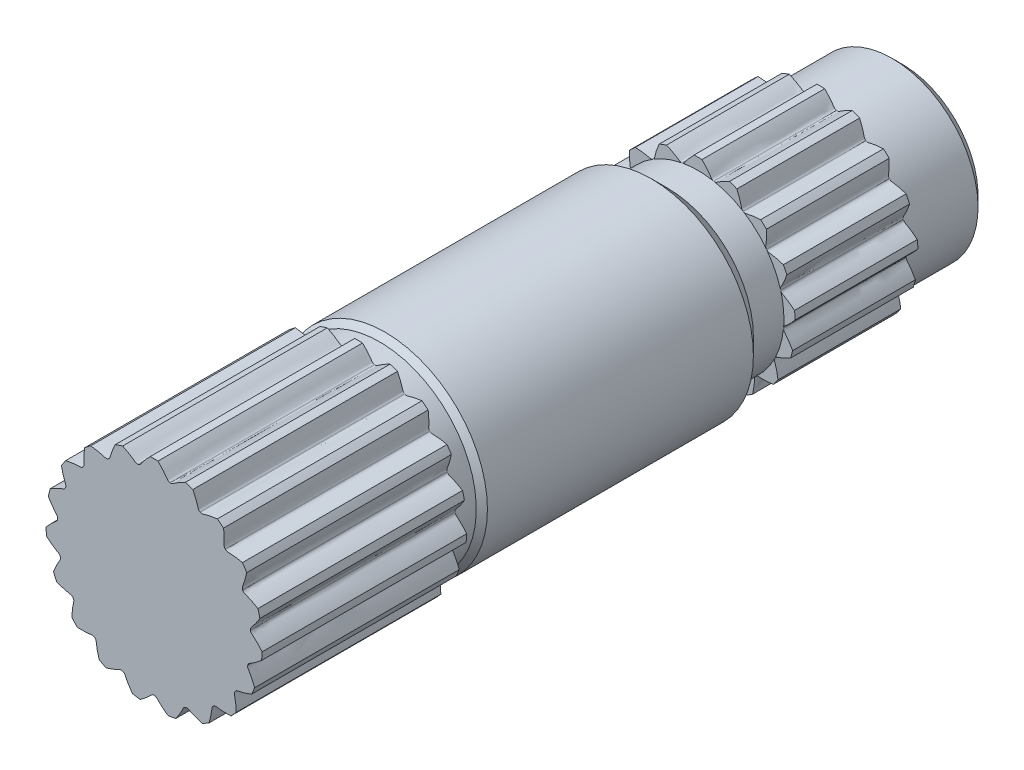
SolidWorks part; units mm, degrees
material "Alloy Steel"
ref_plane "Front Plane" through (0, 0, 0) normal (0, 0, 1) x (1, 0, 0)
ref_plane "Top Plane" through (0, 0, 0) normal (0, 1, 0) x (1, 0, 0)
ref_plane "Right Plane" through (0, 0, 0) normal (1, 0, 0) x (0, 0, -1)
sketch "Sketch12" plane through (0, 0, 0) normal (0, 0, 1) x (1, 0, 0)
  circle A0 centre (0, 0) radius 10
  dimension "D1" = 20
extrude "Boss-Extrude5" add sketch "Sketch12" along normal mid plane 30
sketch "Sketch13" plane through (0, 0, 15) normal (0, 0, 1) x (1, 0, 0)
  circle A0 centre (0, 0) radius 9.4556
  dimension "D1" = 18.9113
extrude "Boss-Extrude6" add sketch "Sketch13" along normal blind 1.587
sketch "Sketch14" plane through (0, 0, -15) normal (0, 0, -1) x (-1, 0, 0)
  circle A0 centre (0, 0) radius 8.3981
  dimension "D1" = 16.7963
extrude "Boss-Extrude7" add sketch "Sketch14" along normal blind 1.587
sketch "Sketch15" plane through (0, 0, 16.587) normal (0, 0, 1) x (1, 0, 0)
  line L0 (5.7898, -7.4758) -> (5.8078, -7.4618)
  line L1 (5.8078, -7.4618) -> (5.8257, -7.4478)
  line L2 (7.9035, -5.1908) -> (7.9159, -5.1717)
  line L3 (7.9159, -5.1717) -> (7.9284, -5.1527)
  line L4 (9.1607, -2.3432) -> (9.1663, -2.3212)
  line L5 (9.1663, -2.3212) -> (9.1719, -2.2992)
  line L6 (9.4252, 0.7582) -> (9.4233, 0.7808)
  line L7 (9.4233, 0.7808) -> (9.4214, 0.8035)
  line L8 (8.6683, 3.7775) -> (8.6592, 3.7983)
  line L9 (8.6592, 3.7983) -> (8.6501, 3.8191)
  line L10 (6.9721, 6.3874) -> (6.9567, 6.4041)
  line L11 (6.9567, 6.4041) -> (6.9413, 6.4208)
  line L12 (4.5204, 8.3051) -> (4.5004, 8.316)
  line L13 (4.5004, 8.316) -> (4.4804, 8.3268)
  line L14 (1.5788, 9.3229) -> (1.5563, 9.3267)
  line L15 (1.5563, 9.3267) -> (1.5339, 9.3304)
  line L16 (-1.5339, 9.3304) -> (-1.5563, 9.3267)
  line L17 (-1.5563, 9.3267) -> (-1.5788, 9.3229)
  line L18 (-4.4804, 8.3268) -> (-4.5004, 8.316)
  line L19 (-4.5004, 8.316) -> (-4.5204, 8.3051)
  line L20 (-6.9413, 6.4208) -> (-6.9567, 6.4041)
  line L21 (-6.9567, 6.4041) -> (-6.9721, 6.3874)
  line L22 (-8.6501, 3.8191) -> (-8.6592, 3.7983)
  line L23 (-8.6592, 3.7983) -> (-8.6683, 3.7775)
  line L24 (-9.4214, 0.8035) -> (-9.4233, 0.7808)
  line L25 (-9.4233, 0.7808) -> (-9.4252, 0.7582)
  line L26 (-9.1719, -2.2992) -> (-9.1663, -2.3212)
  line L27 (-9.1663, -2.3212) -> (-9.1607, -2.3432)
  line L28 (-7.9284, -5.1527) -> (-7.9159, -5.1717)
  line L29 (-7.9159, -5.1717) -> (-7.9035, -5.1908)
  line L30 (-5.8257, -7.4478) -> (-5.8078, -7.4618)
  line L31 (-5.8078, -7.4618) -> (-5.7898, -7.4758)
  line L32 (-3.0917, -8.9359) -> (-3.0702, -8.9433)
  line L33 (-3.0702, -8.9433) -> (-3.0487, -8.9507)
  line L34 (-0.0227, -9.4556) -> (0, -9.4556)
  line L35 (0, -9.4556) -> (0.0227, -9.4556)
  line L36 (3.0487, -8.9507) -> (3.0702, -8.9433)
  line L37 (3.0702, -8.9433) -> (3.0917, -8.9359)
  arc A0 (4.6925, -9.4774) -> (5.3676, -9.1121) centre (0, 0) ccw
  arc A1 (7.5156, -7.4402) -> (8.0355, -6.8755) centre (0, 0) ccw
  arc A2 (9.5242, -4.5968) -> (9.8326, -3.8939) centre (0, 0) ccw
  arc A3 (10.5007, -1.2552) -> (10.5641, -0.4903) centre (0, 0) ccw
  arc A4 (10.3394, 2.2224) -> (10.1509, 2.9665) centre (0, 0) ccw
  arc A5 (9.0575, 5.4591) -> (8.6377, 6.1017) centre (0, 0) ccw
  arc A6 (6.7942, 8.1043) -> (6.1885, 8.5758) centre (0, 0) ccw
  arc A7 (3.7946, 9.8713) -> (3.0686, 10.1205) centre (0, 0) ccw
  arc A8 (0.3838, 10.5685) -> (-0.3838, 10.5685) centre (0, 0) ccw
  arc A9 (-3.0686, 10.1205) -> (-3.7946, 9.8713) centre (0, 0) ccw
  arc A10 (-6.1885, 8.5758) -> (-6.7942, 8.1043) centre (0, 0) ccw
  arc A11 (-8.6377, 6.1017) -> (-9.0575, 5.4591) centre (0, 0) ccw
  arc A12 (-10.1509, 2.9665) -> (-10.3394, 2.2224) centre (0, 0) ccw
  arc A13 (-10.5641, -0.4903) -> (-10.5007, -1.2552) centre (0, 0) ccw
  arc A14 (-9.8326, -3.8939) -> (-9.5242, -4.5968) centre (0, 0) ccw
  arc A15 (-8.0355, -6.8755) -> (-7.5156, -7.4402) centre (0, 0) ccw
  arc A16 (-5.3676, -9.1121) -> (-4.6925, -9.4774) centre (0, 0) ccw
  arc A17 (-2.1181, -10.3612) -> (-1.361, -10.4876) centre (0, 0) ccw
  arc A18 (1.361, -10.4876) -> (2.1181, -10.3612) centre (0, 0) ccw
  spline S0 degree 3 poles (3.0917, -8.9359) (3.1544, -8.9142) (3.2184, -8.911) (3.3396, -8.938) (3.397, -8.9729) (3.5767, -9.0624) (3.828, -9.1783) (4.24, -9.3384) (4.5379, -9.4334) (4.6925, -9.4774) knots 0 0 0 0 0.125 0.125 0.25 0.25 0.5 0.75 1 1 1 1
  spline S1 degree 3 poles (5.3676, -9.1121) (5.4153, -8.9586) (5.4987, -8.6572) (5.5901, -8.2247) (5.6305, -7.951) (5.6538, -7.7516) (5.656, -7.6845) (5.6997, -7.5682) (5.7374, -7.5164) (5.7898, -7.4758) knots 0 0 0 0 0.25 0.5 0.75 0.75 0.875 0.875 1 1 1 1
  spline S2 degree 3 poles (5.8257, -7.4478) (5.8779, -7.407) (5.9374, -7.3832) (6.0608, -7.3694) (6.1265, -7.3837) (6.3255, -7.41) (6.6008, -7.438) (7.0425, -7.4557) (7.3551, -7.4488) (7.5156, -7.4402) knots 0 0 0 0 0.125 0.125 0.25 0.25 0.5 0.75 1 1 1 1
  spline S3 degree 3 poles (8.0355, -6.8755) (8.0308, -6.7148) (8.0117, -6.4027) (7.9577, -5.964) (7.9071, -5.692) (7.8645, -5.4958) (7.8447, -5.4316) (7.8483, -5.3075) (7.8671, -5.2462) (7.9035, -5.1908) knots 0 0 0 0 0.25 0.5 0.75 0.75 0.875 0.875 1 1 1 1
  spline S4 degree 3 poles (7.9284, -5.1527) (7.9645, -5.0971) (8.013, -5.0552) (8.1253, -5.0021) (8.192, -4.9944) (8.3888, -4.9546) (8.6583, -4.8918) (9.0817, -4.765) (9.3752, -4.6571) (9.5242, -4.5968) knots 0 0 0 0 0.125 0.125 0.25 0.25 0.5 0.75 1 1 1 1
  spline S5 degree 3 poles (9.8326, -3.8939) (9.7759, -3.7434) (9.6566, -3.4544) (9.4631, -3.057) (9.3268, -2.8161) (9.2228, -2.6445) (9.1833, -2.5901) (9.1463, -2.4716) (9.1443, -2.4075) (9.1607, -2.3432) knots 0 0 0 0 0.25 0.5 0.75 0.75 0.875 0.875 1 1 1 1
  spline S6 degree 3 poles (9.1719, -2.2992) (9.188, -2.2349) (9.2203, -2.1795) (9.3092, -2.0928) (9.3699, -2.0638) (9.543, -1.9624) (9.7775, -1.8154) (10.1368, -1.558) (10.3793, -1.3606) (10.5007, -1.2552) knots 0 0 0 0 0.125 0.125 0.25 0.25 0.5 0.75 1 1 1 1
  spline S7 degree 3 poles (10.5641, -0.4903) (10.4617, -0.3663) (10.255, -0.1317) (9.9429, 0.1813) (9.7359, 0.3649) (9.5818, 0.4935) (9.5267, 0.532) (9.4533, 0.6322) (9.4305, 0.6921) (9.4252, 0.7582) knots 0 0 0 0 0.25 0.5 0.75 0.75 0.875 0.875 1 1 1 1
  spline S8 degree 3 poles (9.4214, 0.8035) (9.4158, 0.8695) (9.4284, 0.9324) (9.4844, 1.0433) (9.5323, 1.0904) (9.6631, 1.2426) (9.8372, 1.4577) (10.0935, 1.8179) (10.2588, 2.0833) (10.3394, 2.2224) knots 0 0 0 0 0.125 0.125 0.25 0.25 0.5 0.75 1 1 1 1
  spline S9 degree 3 poles (10.1509, 2.9665) (10.0138, 3.0504) (9.7422, 3.2052) (9.3453, 3.4) (9.0899, 3.5063) (8.9024, 3.5779) (8.8378, 3.5965) (8.7358, 3.6674) (8.6948, 3.7167) (8.6683, 3.7775) knots 0 0 0 0 0.25 0.5 0.75 0.75 0.875 0.875 1 1 1 1
  spline S10 degree 3 poles (8.6501, 3.8191) (8.6233, 3.8797) (8.6148, 3.9433) (8.6317, 4.0663) (8.6618, 4.1264) (8.7361, 4.3129) (8.8308, 4.5729) (8.9563, 4.9967) (9.0265, 5.3014) (9.0575, 5.4591) knots 0 0 0 0 0.125 0.125 0.25 0.25 0.5 0.75 1 1 1 1
  spline S11 degree 3 poles (8.6377, 6.1017) (8.4808, 6.1366) (8.1736, 6.1948) (7.735, 6.2502) (7.4588, 6.2678) (7.2583, 6.2747) (7.1911, 6.2713) (7.0717, 6.3052) (7.0169, 6.3385) (6.9721, 6.3874) knots 0 0 0 0 0.25 0.5 0.75 0.75 0.875 0.875 1 1 1 1
  spline S12 degree 3 poles (6.9413, 6.4208) (6.8963, 6.4695) (6.8676, 6.5268) (6.8437, 6.6487) (6.8526, 6.7153) (6.8624, 6.9158) (6.8676, 7.1925) (6.8486, 7.6341) (6.816, 7.9451) (6.7942, 8.1043) knots 0 0 0 0 0.125 0.125 0.25 0.25 0.5 0.75 1 1 1 1
  spline S13 degree 3 poles (6.1885, 8.5758) (6.0287, 8.5578) (5.7193, 8.5131) (5.2865, 8.4231) (5.0196, 8.3501) (4.8276, 8.2914) (4.7652, 8.2664) (4.6412, 8.2597) (4.5786, 8.2734) (4.5204, 8.3051) knots 0 0 0 0 0.25 0.5 0.75 0.75 0.875 0.875 1 1 1 1
  spline S14 degree 3 poles (4.4804, 8.3268) (4.422, 8.3582) (4.3763, 8.4031) (4.3141, 8.5106) (4.3009, 8.5765) (4.245, 8.7693) (4.1601, 9.0326) (3.9988, 9.4442) (3.8669, 9.7277) (3.7946, 9.8713) knots 0 0 0 0 0.125 0.125 0.25 0.25 0.5 0.75 1 1 1 1
  spline S15 degree 3 poles (3.0686, 10.1205) (2.9233, 10.0517) (2.6452, 9.9089) (2.2651, 9.6832) (2.0363, 9.5275) (1.8738, 9.4097) (1.8229, 9.3658) (1.7078, 9.3192) (1.6441, 9.3118) (1.5788, 9.3229) knots 0 0 0 0 0.25 0.5 0.75 0.75 0.875 0.875 1 1 1 1
  spline S16 degree 3 poles (1.5339, 9.3304) (1.4685, 9.3411) (1.4107, 9.3688) (1.3169, 9.4502) (1.283, 9.5083) (1.1676, 9.6725) (1.0018, 9.894) (0.7156, 10.2309) (0.4988, 10.4563) (0.3838, 10.5685) knots 0 0 0 0 0.125 0.125 0.25 0.25 0.5 0.75 1 1 1 1
  spline S17 degree 3 poles (-0.3838, 10.5685) (-0.4988, 10.4563) (-0.7156, 10.2309) (-1.0018, 9.894) (-1.1676, 9.6725) (-1.283, 9.5083) (-1.3169, 9.4502) (-1.4107, 9.3688) (-1.4685, 9.3411) (-1.5339, 9.3304) knots 0 0 0 0 0.25 0.5 0.75 0.75 0.875 0.875 1 1 1 1
  spline S18 degree 3 poles (-1.5788, 9.3229) (-1.6441, 9.3118) (-1.7078, 9.3192) (-1.8229, 9.3658) (-1.8738, 9.4097) (-2.0363, 9.5275) (-2.2651, 9.6832) (-2.6452, 9.9089) (-2.9233, 10.0517) (-3.0686, 10.1205) knots 0 0 0 0 0.125 0.125 0.25 0.25 0.5 0.75 1 1 1 1
  spline S19 degree 3 poles (-3.7946, 9.8713) (-3.8669, 9.7277) (-3.9988, 9.4442) (-4.1601, 9.0326) (-4.245, 8.7693) (-4.3009, 8.5765) (-4.3141, 8.5106) (-4.3763, 8.4031) (-4.422, 8.3582) (-4.4804, 8.3268) knots 0 0 0 0 0.25 0.5 0.75 0.75 0.875 0.875 1 1 1 1
  spline S20 degree 3 poles (-4.5204, 8.3051) (-4.5786, 8.2734) (-4.6412, 8.2597) (-4.7652, 8.2664) (-4.8276, 8.2914) (-5.0196, 8.3501) (-5.2865, 8.4231) (-5.7193, 8.5131) (-6.0287, 8.5578) (-6.1885, 8.5758) knots 0 0 0 0 0.125 0.125 0.25 0.25 0.5 0.75 1 1 1 1
  spline S21 degree 3 poles (-6.7942, 8.1043) (-6.816, 7.9451) (-6.8486, 7.6341) (-6.8676, 7.1925) (-6.8624, 6.9158) (-6.8526, 6.7153) (-6.8437, 6.6487) (-6.8676, 6.5268) (-6.8963, 6.4695) (-6.9413, 6.4208) knots 0 0 0 0 0.25 0.5 0.75 0.75 0.875 0.875 1 1 1 1
  spline S22 degree 3 poles (-6.9721, 6.3874) (-7.0169, 6.3385) (-7.0717, 6.3052) (-7.1911, 6.2713) (-7.2583, 6.2747) (-7.4588, 6.2678) (-7.735, 6.2502) (-8.1736, 6.1948) (-8.4808, 6.1366) (-8.6377, 6.1017) knots 0 0 0 0 0.125 0.125 0.25 0.25 0.5 0.75 1 1 1 1
  spline S23 degree 3 poles (-9.0575, 5.4591) (-9.0265, 5.3014) (-8.9563, 4.9967) (-8.8308, 4.5729) (-8.7361, 4.3129) (-8.6618, 4.1264) (-8.6317, 4.0663) (-8.6148, 3.9433) (-8.6233, 3.8797) (-8.6501, 3.8191) knots 0 0 0 0 0.25 0.5 0.75 0.75 0.875 0.875 1 1 1 1
  spline S24 degree 3 poles (-8.6683, 3.7775) (-8.6948, 3.7167) (-8.7358, 3.6674) (-8.8378, 3.5965) (-8.9024, 3.5779) (-9.0899, 3.5063) (-9.3453, 3.4) (-9.7422, 3.2052) (-10.0138, 3.0504) (-10.1509, 2.9665) knots 0 0 0 0 0.125 0.125 0.25 0.25 0.5 0.75 1 1 1 1
  spline S25 degree 3 poles (-10.3394, 2.2224) (-10.2588, 2.0833) (-10.0935, 1.8179) (-9.8372, 1.4577) (-9.6631, 1.2426) (-9.5323, 1.0904) (-9.4844, 1.0433) (-9.4284, 0.9324) (-9.4158, 0.8695) (-9.4214, 0.8035) knots 0 0 0 0 0.25 0.5 0.75 0.75 0.875 0.875 1 1 1 1
  spline S26 degree 3 poles (-9.4252, 0.7582) (-9.4305, 0.6921) (-9.4533, 0.6322) (-9.5267, 0.532) (-9.5818, 0.4935) (-9.7359, 0.3649) (-9.9429, 0.1813) (-10.255, -0.1317) (-10.4617, -0.3663) (-10.5641, -0.4903) knots 0 0 0 0 0.125 0.125 0.25 0.25 0.5 0.75 1 1 1 1
  spline S27 degree 3 poles (-10.5007, -1.2552) (-10.3793, -1.3606) (-10.1368, -1.558) (-9.7775, -1.8154) (-9.543, -1.9624) (-9.3699, -2.0638) (-9.3092, -2.0928) (-9.2203, -2.1795) (-9.188, -2.2349) (-9.1719, -2.2992) knots 0 0 0 0 0.25 0.5 0.75 0.75 0.875 0.875 1 1 1 1
  spline S28 degree 3 poles (-9.1607, -2.3432) (-9.1443, -2.4075) (-9.1463, -2.4716) (-9.1833, -2.5901) (-9.2228, -2.6445) (-9.3268, -2.8161) (-9.4631, -3.057) (-9.6566, -3.4544) (-9.7759, -3.7434) (-9.8326, -3.8939) knots 0 0 0 0 0.125 0.125 0.25 0.25 0.5 0.75 1 1 1 1
  spline S29 degree 3 poles (-9.5242, -4.5968) (-9.3752, -4.6571) (-9.0817, -4.765) (-8.6583, -4.8918) (-8.3888, -4.9546) (-8.192, -4.9944) (-8.1253, -5.0021) (-8.013, -5.0552) (-7.9645, -5.0971) (-7.9284, -5.1527) knots 0 0 0 0 0.25 0.5 0.75 0.75 0.875 0.875 1 1 1 1
  spline S30 degree 3 poles (-7.9035, -5.1908) (-7.8671, -5.2462) (-7.8483, -5.3075) (-7.8447, -5.4316) (-7.8645, -5.4958) (-7.9071, -5.692) (-7.9577, -5.964) (-8.0117, -6.4027) (-8.0308, -6.7148) (-8.0355, -6.8755) knots 0 0 0 0 0.125 0.125 0.25 0.25 0.5 0.75 1 1 1 1
  spline S31 degree 3 poles (-7.5156, -7.4402) (-7.3551, -7.4488) (-7.0425, -7.4557) (-6.6008, -7.438) (-6.3255, -7.41) (-6.1265, -7.3837) (-6.0608, -7.3694) (-5.9374, -7.3832) (-5.8779, -7.407) (-5.8257, -7.4478) knots 0 0 0 0 0.25 0.5 0.75 0.75 0.875 0.875 1 1 1 1
  spline S32 degree 3 poles (-5.7898, -7.4758) (-5.7374, -7.5164) (-5.6997, -7.5682) (-5.656, -7.6845) (-5.6538, -7.7516) (-5.6305, -7.951) (-5.5901, -8.2247) (-5.4987, -8.6572) (-5.4153, -8.9586) (-5.3676, -9.1121) knots 0 0 0 0 0.125 0.125 0.25 0.25 0.5 0.75 1 1 1 1
  spline S33 degree 3 poles (-4.6925, -9.4774) (-4.5379, -9.4334) (-4.24, -9.3384) (-3.828, -9.1783) (-3.5767, -9.0624) (-3.397, -8.9729) (-3.3396, -8.938) (-3.2184, -8.911) (-3.1544, -8.9142) (-3.0917, -8.9359) knots 0 0 0 0 0.25 0.5 0.75 0.75 0.875 0.875 1 1 1 1
  spline S34 degree 3 poles (-3.0487, -8.9507) (-2.986, -8.972) (-2.9335, -9.0088) (-2.8544, -9.1046) (-2.8306, -9.1674) (-2.7437, -9.3484) (-2.6166, -9.5942) (-2.3898, -9.9736) (-2.2131, -10.2315) (-2.1181, -10.3612) knots 0 0 0 0 0.125 0.125 0.25 0.25 0.5 0.75 1 1 1 1
  spline S35 degree 3 poles (-1.361, -10.4876) (-1.229, -10.3957) (-0.9781, -10.2091) (-0.6404, -9.9239) (-0.4404, -9.7327) (-0.2995, -9.5898) (-0.2565, -9.5381) (-0.1506, -9.4732) (-0.089, -9.4555) (-0.0227, -9.4556) knots 0 0 0 0 0.25 0.5 0.75 0.75 0.875 0.875 1 1 1 1
  spline S36 degree 3 poles (0.0227, -9.4556) (0.089, -9.4555) (0.1506, -9.4732) (0.2565, -9.5381) (0.2995, -9.5898) (0.4404, -9.7327) (0.6404, -9.9239) (0.9781, -10.2091) (1.229, -10.3957) (1.361, -10.4876) knots 0 0 0 0 0.125 0.125 0.25 0.25 0.5 0.75 1 1 1 1
  spline S37 degree 3 poles (2.1181, -10.3612) (2.2131, -10.2315) (2.3898, -9.9736) (2.6166, -9.5942) (2.7437, -9.3484) (2.8306, -9.1674) (2.8544, -9.1046) (2.9335, -9.0088) (2.986, -8.972) (3.0487, -8.9507) knots 0 0 0 0 0.25 0.5 0.75 0.75 0.875 0.875 1 1 1 1
extrude "Boss-Extrude8" add sketch "Sketch15" along normal blind 20
sketch "Sketch17" plane through (0, 0, -16.587) normal (0, 0, -1) x (-1, 0, 0)
  line L38 (4.4402, 7.1283) -> (4.4211, 7.1402)
  line L39 (4.4211, 7.1402) -> (4.4019, 7.1521)
  line L40 (1.5653, 8.251) -> (1.5432, 8.2552)
  line L41 (1.5432, 8.2552) -> (1.521, 8.2593)
  line L42 (-1.521, 8.2593) -> (-1.5432, 8.2552)
  line L43 (-1.5432, 8.2552) -> (-1.5653, 8.251)
  line L44 (-4.4019, 7.1521) -> (-4.4211, 7.1402)
  line L45 (-4.4211, 7.1402) -> (-4.4402, 7.1283)
  line L46 (-6.6882, 5.079) -> (-6.7019, 5.061)
  line L47 (-6.7019, 5.061) -> (-6.7154, 5.043)
  line L48 (-8.0713, 2.32) -> (-8.0776, 2.2983)
  line L49 (-8.0776, 2.2983) -> (-8.0837, 2.2766)
  line L50 (-8.3644, -0.7524) -> (-8.3623, -0.7749)
  line L51 (-8.3623, -0.7749) -> (-8.3602, -0.7973)
  line L52 (-7.5277, -3.7232) -> (-7.5177, -3.7434)
  line L53 (-7.5177, -3.7434) -> (-7.5076, -3.7636)
  line L54 (-5.6744, -6.1911) -> (-5.6578, -6.2063)
  line L55 (-5.6578, -6.2063) -> (-5.6411, -6.2215)
  line L56 (-3.0548, -7.8229) -> (-3.0338, -7.831)
  line L57 (-3.0338, -7.831) -> (-3.0127, -7.8392)
  line L58 (-0.0226, -8.3981) -> (0, -8.3981)
  line L59 (0, -8.3981) -> (0.0226, -8.3981)
  line L60 (3.0127, -7.8392) -> (3.0338, -7.831)
  line L61 (3.0338, -7.831) -> (3.0548, -7.8229)
  line L62 (5.6411, -6.2215) -> (5.6578, -6.2063)
  line L63 (5.6578, -6.2063) -> (5.6744, -6.1911)
  line L64 (7.5076, -3.7636) -> (7.5177, -3.7434)
  line L65 (7.5177, -3.7434) -> (7.5277, -3.7232)
  line L66 (8.3602, -0.7973) -> (8.3623, -0.7749)
  line L67 (8.3623, -0.7749) -> (8.3644, -0.7524)
  line L68 (8.0837, 2.2766) -> (8.0776, 2.2983)
  line L69 (8.0776, 2.2983) -> (8.0713, 2.32)
  line L70 (6.7154, 5.043) -> (6.7019, 5.061)
  line L71 (6.7019, 5.061) -> (6.6882, 5.079)
  arc A19 (6.6912, 6.7683) -> (6.1221, 7.2872) centre (0, 0) ccw
  arc A20 (3.7944, 8.7284) -> (3.0762, 9.0066) centre (0, 0) ccw
  arc A21 (0.3851, 9.5097) -> (-0.3851, 9.5097) centre (0, 0) ccw
  arc A22 (-3.0762, 9.0066) -> (-3.7944, 8.7284) centre (0, 0) ccw
  arc A23 (-6.1221, 7.2872) -> (-6.6912, 6.7683) centre (0, 0) ccw
  arc A24 (-8.3411, 4.5835) -> (-8.6844, 3.8941) centre (0, 0) ccw
  arc A25 (-9.4336, 1.2609) -> (-9.5047, 0.494) centre (0, 0) ccw
  arc A26 (-9.2521, -2.2321) -> (-9.0413, -2.9728) centre (0, 0) ccw
  arc A27 (-7.821, -5.4236) -> (-7.3569, -6.0382) centre (0, 0) ccw
  arc A28 (-5.3336, -7.8826) -> (-4.6788, -8.288) centre (0, 0) ccw
  arc A29 (-2.1259, -9.277) -> (-1.3689, -9.4185) centre (0, 0) ccw
  arc A30 (1.3689, -9.4185) -> (2.1259, -9.277) centre (0, 0) ccw
  arc A31 (4.6788, -8.288) -> (5.3336, -7.8826) centre (0, 0) ccw
  arc A32 (7.3569, -6.0382) -> (7.821, -5.4236) centre (0, 0) ccw
  arc A33 (9.0413, -2.9728) -> (9.2521, -2.2321) centre (0, 0) ccw
  arc A34 (9.5047, 0.494) -> (9.4336, 1.2609) centre (0, 0) ccw
  arc A35 (8.6844, 3.8941) -> (8.3411, 4.5835) centre (0, 0) ccw
  spline S0 degree 3 poles (6.6882, 5.079) (6.6486, 5.1312) (6.6257, 5.1903) (6.6128, 5.3124) (6.6277, 5.3769) (6.657, 5.5736) (6.6884, 5.8472) (6.7084, 6.2901) (6.7009, 6.6058) (6.6912, 6.7683) knots 0 0 0 0 0.125 0.125 0.25 0.25 0.5 0.75 1 1 1 1 weights 1 1 1 1 1 1 1 1 1 1
  spline S1 degree 3 poles (6.1221, 7.2872) (5.9593, 7.2818) (5.6443, 7.2602) (5.2052, 7.1994) (4.9356, 7.1428) (4.7425, 7.0956) (4.6796, 7.0748) (4.5569, 7.0763) (4.4958, 7.0937) (4.4402, 7.1283) knots 0 0 0 0 0.25 0.5 0.75 0.75 0.875 0.875 1 1 1 1 weights 1 1 1 1 1 1 1 1 1 1
  spline S2 degree 3 poles (4.4019, 7.1521) (4.3461, 7.1864) (4.3033, 7.2333) (4.2472, 7.3425) (4.2378, 7.4081) (4.194, 7.602) (4.1245, 7.8685) (3.9832, 8.2887) (3.8621, 8.5804) (3.7944, 8.7284) knots 0 0 0 0 0.125 0.125 0.25 0.25 0.5 0.75 1 1 1 1 weights 1 1 1 1 1 1 1 1 1 1
  spline S3 degree 3 poles (3.0762, 9.0066) (2.9264, 8.9428) (2.6405, 8.8089) (2.253, 8.5935) (2.022, 8.4434) (1.859, 8.3296) (1.8079, 8.2875) (1.6929, 8.2446) (1.6297, 8.2388) (1.5653, 8.251) knots 0 0 0 0 0.25 0.5 0.75 0.75 0.875 0.875 1 1 1 1 weights 1 1 1 1 1 1 1 1 1 1
  spline S4 degree 3 poles (1.521, 8.2593) (1.4566, 8.2711) (1.3997, 8.2994) (1.308, 8.3809) (1.2755, 8.4387) (1.1646, 8.6037) (1.0035, 8.8271) (0.7199, 9.1679) (0.5017, 9.3961) (0.3851, 9.5097) knots 0 0 0 0 0.125 0.125 0.25 0.25 0.5 0.75 1 1 1 1 weights 1 1 1 1 1 1 1 1 1 1
  spline S5 degree 3 poles (-0.3851, 9.5097) (-0.5017, 9.3961) (-0.7199, 9.1679) (-1.0035, 8.8271) (-1.1646, 8.6037) (-1.2755, 8.4387) (-1.308, 8.3809) (-1.3997, 8.2994) (-1.4566, 8.2711) (-1.521, 8.2593) knots 0 0 0 0 0.25 0.5 0.75 0.75 0.875 0.875 1 1 1 1 weights 1 1 1 1 1 1 1 1 1 1
  spline S6 degree 3 poles (-1.5653, 8.251) (-1.6297, 8.2388) (-1.6929, 8.2446) (-1.8079, 8.2875) (-1.859, 8.3296) (-2.022, 8.4434) (-2.253, 8.5935) (-2.6405, 8.8089) (-2.9264, 8.9428) (-3.0762, 9.0066) knots 0 0 0 0 0.125 0.125 0.25 0.25 0.5 0.75 1 1 1 1 weights 1 1 1 1 1 1 1 1 1 1
  spline S7 degree 3 poles (-3.7944, 8.7284) (-3.8621, 8.5804) (-3.9832, 8.2887) (-4.1245, 7.8685) (-4.194, 7.602) (-4.2378, 7.4081) (-4.2472, 7.3425) (-4.3033, 7.2333) (-4.3461, 7.1864) (-4.4019, 7.1521) knots 0 0 0 0 0.25 0.5 0.75 0.75 0.875 0.875 1 1 1 1 weights 1 1 1 1 1 1 1 1 1 1
  spline S8 degree 3 poles (-4.4402, 7.1283) (-4.4958, 7.0937) (-4.5569, 7.0763) (-4.6796, 7.0748) (-4.7425, 7.0956) (-4.9356, 7.1428) (-5.2052, 7.1994) (-5.6443, 7.2602) (-5.9593, 7.2818) (-6.1221, 7.2872) knots 0 0 0 0 0.125 0.125 0.25 0.25 0.5 0.75 1 1 1 1 weights 1 1 1 1 1 1 1 1 1 1
  spline S9 degree 3 poles (-6.6912, 6.7683) (-6.7009, 6.6058) (-6.7084, 6.2901) (-6.6884, 5.8472) (-6.657, 5.5736) (-6.6277, 5.3769) (-6.6128, 5.3124) (-6.6257, 5.1903) (-6.6486, 5.1312) (-6.6882, 5.079) knots 0 0 0 0 0.25 0.5 0.75 0.75 0.875 0.875 1 1 1 1 weights 1 1 1 1 1 1 1 1 1 1
  spline S10 degree 3 poles (-6.7154, 5.043) (-6.7548, 4.9906) (-6.8054, 4.9523) (-6.9193, 4.9066) (-6.9854, 4.9033) (-7.1826, 4.8775) (-7.4544, 4.8329) (-7.8859, 4.7309) (-8.1874, 4.6373) (-8.3411, 4.5835) knots 0 0 0 0 0.125 0.125 0.25 0.25 0.5 0.75 1 1 1 1 weights 1 1 1 1 1 1 1 1 1 1
  spline S11 degree 3 poles (-8.6844, 3.8941) (-8.6347, 3.7391) (-8.5277, 3.442) (-8.349, 3.0363) (-8.2209, 2.7925) (-8.1225, 2.6196) (-8.0853, 2.5648) (-8.0532, 2.4464) (-8.0533, 2.3829) (-8.0713, 2.32) knots 0 0 0 0 0.25 0.5 0.75 0.75 0.875 0.875 1 1 1 1 weights 1 1 1 1 1 1 1 1 1 1
  spline S12 degree 3 poles (-8.0837, 2.2766) (-8.1015, 2.2135) (-8.1348, 2.1595) (-8.2245, 2.0757) (-8.285, 2.0487) (-8.4596, 1.9535) (-8.6968, 1.8137) (-9.0624, 1.5628) (-9.3097, 1.3665) (-9.4336, 1.2609) knots 0 0 0 0 0.125 0.125 0.25 0.25 0.5 0.75 1 1 1 1 weights 1 1 1 1 1 1 1 1 1 1
  spline S13 degree 3 poles (-9.5047, 0.494) (-9.4023, 0.3674) (-9.1952, 0.129) (-8.882, -0.1848) (-8.6745, -0.3658) (-8.5204, -0.4915) (-8.4659, -0.5291) (-8.3931, -0.628) (-8.3702, -0.6872) (-8.3644, -0.7524) knots 0 0 0 0 0.25 0.5 0.75 0.75 0.875 0.875 1 1 1 1 weights 1 1 1 1 1 1 1 1 1 1
  spline S14 degree 3 poles (-8.3602, -0.7973) (-8.354, -0.8625) (-8.3656, -0.925) (-8.419, -1.0355) (-8.4656, -1.0825) (-8.594, -1.2344) (-8.7647, -1.4504) (-9.0149, -1.8164) (-9.1747, -2.0888) (-9.2521, -2.2321) knots 0 0 0 0 0.125 0.125 0.25 0.25 0.5 0.75 1 1 1 1 weights 1 1 1 1 1 1 1 1 1 1
  spline S15 degree 3 poles (-9.0413, -2.9728) (-8.9001, -3.0539) (-8.6209, -3.2014) (-8.2155, -3.3809) (-7.9566, -3.4747) (-7.7675, -3.5362) (-7.7031, -3.5516) (-7.5995, -3.6175) (-7.5568, -3.6645) (-7.5277, -3.7232) knots 0 0 0 0 0.25 0.5 0.75 0.75 0.875 0.875 1 1 1 1 weights 1 1 1 1 1 1 1 1 1 1
  spline S16 degree 3 poles (-7.5076, -3.7636) (-7.4783, -3.8221) (-7.4666, -3.8845) (-7.4764, -4.0068) (-7.5029, -4.0675) (-7.5678, -4.2555) (-7.6489, -4.5187) (-7.75, -4.9504) (-7.8006, -5.262) (-7.821, -5.4236) knots 0 0 0 0 0.125 0.125 0.25 0.25 0.5 0.75 1 1 1 1 weights 1 1 1 1 1 1 1 1 1 1
  spline S17 degree 3 poles (-7.3569, -6.0382) (-7.1959, -6.0628) (-6.8823, -6.0994) (-6.4394, -6.1203) (-6.1641, -6.1143) (-5.9655, -6.1033) (-5.8999, -6.0945) (-5.7795, -6.1185) (-5.7227, -6.1468) (-5.6744, -6.1911) knots 0 0 0 0 0.25 0.5 0.75 0.75 0.875 0.875 1 1 1 1 weights 1 1 1 1 1 1 1 1 1 1
  spline S18 degree 3 poles (-5.6411, -6.2215) (-5.5926, -6.2655) (-5.5591, -6.3194) (-5.5241, -6.437) (-5.5269, -6.5032) (-5.5195, -6.7019) (-5.5001, -6.9766) (-5.4384, -7.4157) (-5.373, -7.7246) (-5.3336, -7.8826) knots 0 0 0 0 0.125 0.125 0.25 0.25 0.5 0.75 1 1 1 1 weights 1 1 1 1 1 1 1 1 1 1
  spline S19 degree 3 poles (-4.6788, -8.288) (-4.5198, -8.2528) (-4.2142, -8.1737) (-3.7936, -8.0332) (-3.5391, -7.9281) (-3.3579, -7.8462) (-3.2999, -7.8142) (-3.179, -7.7931) (-3.1158, -7.799) (-3.0548, -7.8229) knots 0 0 0 0 0.25 0.5 0.75 0.75 0.875 0.875 1 1 1 1 weights 1 1 1 1 1 1 1 1 1 1
  spline S20 degree 3 poles (-3.0127, -7.8392) (-2.9516, -7.8627) (-2.9009, -7.9009) (-2.8257, -7.9979) (-2.8044, -8.0606) (-2.7257, -8.2432) (-2.6084, -8.4924) (-2.3923, -8.8795) (-2.2197, -9.1439) (-2.1259, -9.277) knots 0 0 0 0 0.125 0.125 0.25 0.25 0.5 0.75 1 1 1 1 weights 1 1 1 1 1 1 1 1 1 1
  spline S21 degree 3 poles (-1.3689, -9.4185) (-1.2333, -9.3283) (-0.9769, -9.1441) (-0.6355, -8.8612) (-0.4361, -8.6712) (-0.2968, -8.5294) (-0.2543, -8.4786) (-0.1491, -8.4153) (-0.0881, -8.3979) (-0.0226, -8.3981) knots 0 0 0 0 0.25 0.5 0.75 0.75 0.875 0.875 1 1 1 1 weights 1 1 1 1 1 1 1 1 1 1
  spline S22 degree 3 poles (0.0226, -8.3981) (0.0881, -8.3979) (0.1491, -8.4153) (0.2543, -8.4786) (0.2968, -8.5294) (0.4361, -8.6712) (0.6355, -8.8612) (0.9769, -9.1441) (1.2333, -9.3283) (1.3689, -9.4185) knots 0 0 0 0 0.125 0.125 0.25 0.25 0.5 0.75 1 1 1 1 weights 1 1 1 1 1 1 1 1 1 1
  spline S23 degree 3 poles (2.1259, -9.277) (2.2197, -9.1439) (2.3923, -8.8795) (2.6084, -8.4924) (2.7257, -8.2432) (2.8044, -8.0606) (2.8257, -7.9979) (2.9009, -7.9009) (2.9516, -7.8627) (3.0127, -7.8392) knots 0 0 0 0 0.25 0.5 0.75 0.75 0.875 0.875 1 1 1 1 weights 1 1 1 1 1 1 1 1 1 1
  spline S24 degree 3 poles (3.0548, -7.8229) (3.1158, -7.799) (3.179, -7.7931) (3.2999, -7.8142) (3.3579, -7.8462) (3.5391, -7.9281) (3.7936, -8.0332) (4.2142, -8.1737) (4.5198, -8.2528) (4.6788, -8.288) knots 0 0 0 0 0.125 0.125 0.25 0.25 0.5 0.75 1 1 1 1 weights 1 1 1 1 1 1 1 1 1 1
  spline S25 degree 3 poles (5.3336, -7.8826) (5.373, -7.7246) (5.4384, -7.4157) (5.5001, -6.9766) (5.5195, -6.7019) (5.5269, -6.5032) (5.5241, -6.437) (5.5591, -6.3194) (5.5926, -6.2655) (5.6411, -6.2215) knots 0 0 0 0 0.25 0.5 0.75 0.75 0.875 0.875 1 1 1 1 weights 1 1 1 1 1 1 1 1 1 1
  spline S26 degree 3 poles (5.6744, -6.1911) (5.7227, -6.1468) (5.7795, -6.1185) (5.8999, -6.0945) (5.9655, -6.1033) (6.1641, -6.1143) (6.4394, -6.1203) (6.8823, -6.0994) (7.1959, -6.0628) (7.3569, -6.0382) knots 0 0 0 0 0.125 0.125 0.25 0.25 0.5 0.75 1 1 1 1 weights 1 1 1 1 1 1 1 1 1 1
  spline S27 degree 3 poles (7.821, -5.4236) (7.8006, -5.262) (7.75, -4.9504) (7.6489, -4.5187) (7.5678, -4.2555) (7.5029, -4.0675) (7.4764, -4.0068) (7.4666, -3.8845) (7.4783, -3.8221) (7.5076, -3.7636) knots 0 0 0 0 0.25 0.5 0.75 0.75 0.875 0.875 1 1 1 1 weights 1 1 1 1 1 1 1 1 1 1
  spline S28 degree 3 poles (7.5277, -3.7232) (7.5568, -3.6645) (7.5995, -3.6175) (7.7031, -3.5516) (7.7675, -3.5362) (7.9566, -3.4747) (8.2155, -3.3809) (8.6209, -3.2014) (8.9001, -3.0539) (9.0413, -2.9728) knots 0 0 0 0 0.125 0.125 0.25 0.25 0.5 0.75 1 1 1 1 weights 1 1 1 1 1 1 1 1 1 1
  spline S29 degree 3 poles (9.2521, -2.2321) (9.1747, -2.0888) (9.0149, -1.8164) (8.7647, -1.4504) (8.594, -1.2344) (8.4656, -1.0825) (8.419, -1.0355) (8.3656, -0.925) (8.354, -0.8625) (8.3602, -0.7973) knots 0 0 0 0 0.25 0.5 0.75 0.75 0.875 0.875 1 1 1 1 weights 1 1 1 1 1 1 1 1 1 1
  spline S30 degree 3 poles (8.3644, -0.7524) (8.3702, -0.6872) (8.3931, -0.628) (8.4659, -0.5291) (8.5204, -0.4915) (8.6745, -0.3658) (8.882, -0.1848) (9.1952, 0.129) (9.4023, 0.3674) (9.5047, 0.494) knots 0 0 0 0 0.125 0.125 0.25 0.25 0.5 0.75 1 1 1 1 weights 1 1 1 1 1 1 1 1 1 1
  spline S31 degree 3 poles (9.4336, 1.2609) (9.3097, 1.3665) (9.0624, 1.5628) (8.6968, 1.8137) (8.4596, 1.9535) (8.285, 2.0487) (8.2245, 2.0757) (8.1348, 2.1595) (8.1015, 2.2135) (8.0837, 2.2766) knots 0 0 0 0 0.25 0.5 0.75 0.75 0.875 0.875 1 1 1 1 weights 1 1 1 1 1 1 1 1 1 1
  spline S32 degree 3 poles (8.0713, 2.32) (8.0533, 2.3829) (8.0532, 2.4464) (8.0853, 2.5648) (8.1225, 2.6196) (8.2209, 2.7925) (8.349, 3.0363) (8.5277, 3.442) (8.6347, 3.7391) (8.6844, 3.8941) knots 0 0 0 0 0.125 0.125 0.25 0.25 0.5 0.75 1 1 1 1 weights 1 1 1 1 1 1 1 1 1 1
  spline S33 degree 3 poles (8.3411, 4.5835) (8.1874, 4.6373) (7.8858, 4.731) (7.4544, 4.8329) (7.1826, 4.8775) (6.9854, 4.9033) (6.9193, 4.9066) (6.8054, 4.9523) (6.7548, 4.9906) (6.7154, 5.043) knots 0 0 0 0 0.25 0.5 0.75 0.75 0.875 0.875 1 1 1 1 weights 1 1 1 1 1 1 1 1 1 1
extrude "Sun Gear Spline" add sketch "Sketch17" along normal blind 12
sketch "Sketch20" plane through (0, 0, -28.587) normal (0, 0, -1) x (-1, 0, 0)
  circle A0 centre (0, 0) radius 8.3981
extrude "Boss-Extrude9" add sketch "Sketch20" along normal blind 7.975
chamfer "Chamfer1" distance 3 angle 45 1 edges at (10, 0, -15)
chamfer "Chamfer2" distance 1 angle 45 1 edges at (-8.3981, 0, -36.562)
chamfer "Chamfer3" distance 1 angle 45 1 edges at (10, 0, 15)
